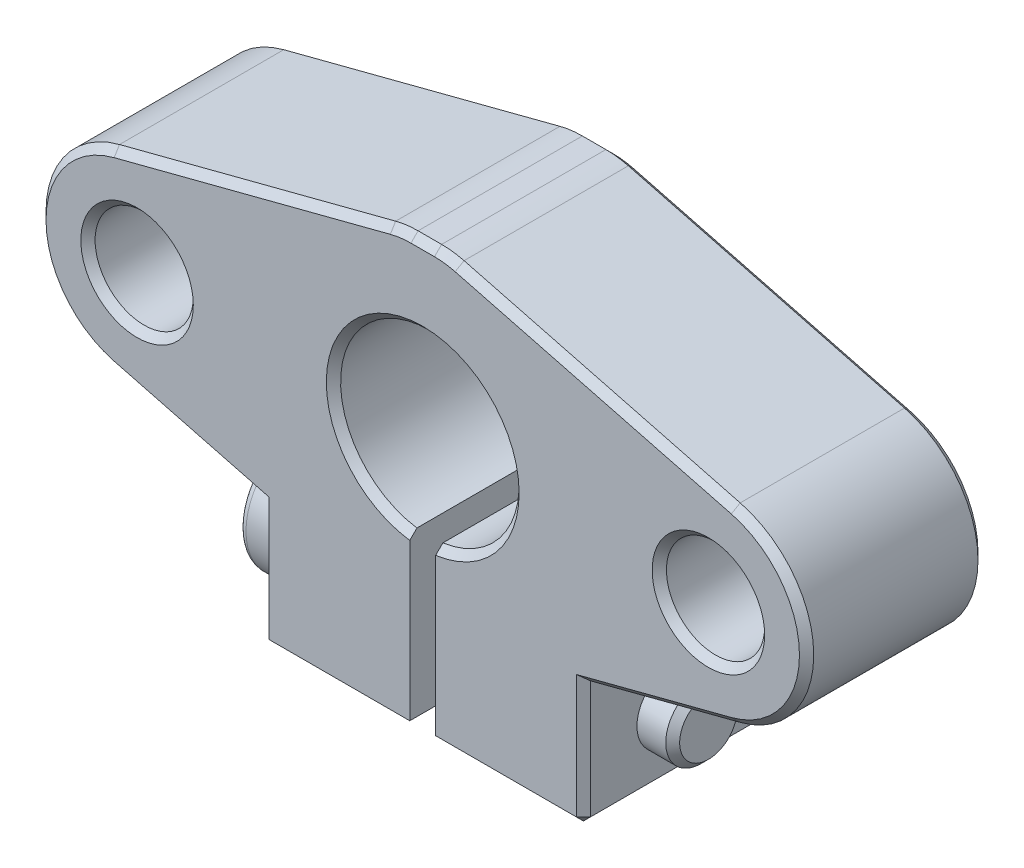
SolidWorks part; units mm, degrees
ref_plane "Спереди" through (0, 0, 0) normal (0, 0, 1) x (1, 0, 0)
ref_plane "Сверху" through (0, 0, 0) normal (0, 1, 0) x (1, 0, 0)
ref_plane "Справа" through (0, 0, 0) normal (1, 0, 0) x (0, 0, -1)
sketch "Эскиз2" plane through (0, 0, 0) normal (0, 0, 1) x (1, 0, 0)
  line L0 (-16, 0) -> (16, 0) construction
  line L1 (9, 7.5) -> (1.2976, 9.5)
  line L2 (9, 7.5) -> (17.3823, 5.3235)
  line L3 (0, 14.1459) -> (0, -18.2907) construction
  line L4 (9, -7.5) -> (17.3823, -5.3235)
  line L5 (-9, -14.5) -> (9, -14.5)
  line L6 (9, -14.5) -> (9, -7.5)
  line L7 (9, -11) -> (-9, -11) construction
  line L8 (1.2976, 9.5) -> (-1.2976, 9.5)
  line L9 (21.5, 0) -> (21.5, -6.4867) construction
  line L10 (0.725, -4.9472) -> (0.725, -14.5)
  line L11 (-21.5, 0) -> (-21.5, -6.4867) construction
  line L12 (-0.725, -4.9472) -> (-0.725, -14.5)
  line L13 (-9, -14.5) -> (-9, -7.5)
  line L14 (-9, -7.5) -> (-17.3823, -5.3235)
  line L15 (-9, 7.5) -> (-17.3823, 5.3235)
  line L16 (-9, 7.5) -> (-1.2976, 9.5)
  circle A0 centre (0, 0) radius 5
  circle A2 centre (16, 0) radius 2.75
  circle A3 centre (16, 0) radius 5.5
  circle A4 centre (-16, 0) radius 5.5
  circle A5 centre (-16, 0) radius 2.75
  point P27 (0, -11)
  point P33 (0, 9.5)
  point P35 (0, -14.5)
  dimension "D2" = 5.5
  dimension "D3" = 11
  dimension "D4" = 10
  dimension "D5" = 16
  dimension "D6" = 9
  dimension "D7" = 11
  dimension "D8" = 24
  dimension "D9" = 21.5
  dimension "D10" = 7
  dimension "D11" = 1.45
extrude "Бобышка-Вытянуть1" add sketch "Эскиз2" along normal blind 10 contours L15 A4 L14 L13 L5 L12 A0 L10 L6 L4 A3 L2 L1 L8 L16 | A3 A2 | A4 A5 region at (13.085, 6.0028, 0) region at (20.2274, 3.2699, 0) region at (-12.7301, 4.2274, 0)
sketch "Эскиз4" plane through (-9, 0, 0) normal (-1, 0, 0) x (0, 0, 1)
  line L0 (0, -14.5) -> (10, -7.5) construction
  circle A0 centre (5, -11) radius 2
  dimension "D1" = 4
fillet "Скругление1" radius 5 2 edges at (-1.2976, 9.5, 5) (1.2976, 9.5, 5)
chamfer "Фаска1" distance 0.4 angle 45 34 edges at (-13.25, 0, 10) (18.75, 0, 10) (0.725, -14.5, 5) (9, -14.5, 5) (-9, -14.5, 5) (-21.5, 0, 0) (-13.1911, -6.4117, 0) (-4.8625, -14.5, 0) (-9.649, 7.3315, 0) (0, 9.5, 0) (9.649, 7.3315, 0) (21.5, 0, 0) (13.1911, -6.4117, 0) (4.8625, -14.5, 0) (0, 5, 0) (-0.725, -14.5, 5) (0, 9.5, 10) (9.649, 7.3315, 10) (21.5, 0, 10) (13.1911, -6.4117, 10) (9, -11, 10) (4.8625, -14.5, 10) (0, 5, 10) (-4.8625, -14.5, 10) (-13.1911, -6.4117, 10) (-21.5, 0, 10) (-9.649, 7.3315, 10) (-1.2924, 9.4597, 0) (1.2924, 9.4597, 0) (1.2924, 9.4597, 10) (-1.2924, 9.4597, 10) (-9, -11, 10) (-13.25, 0, 0) (18.75, 0, 0)
sketch "Эскиз6" plane through (0, 0, 10) normal (0, 0, 1) x (1, 0, 0)
  line L0 (-8.6, -11) -> (-10.2537, -10.0452)
  line L1 (-10.2537, -10.0452) -> (-10.2537, -11.9548)
  line L2 (-10.2537, -11.9548) -> (-8.6, -11)
  line L3 (-9, -14.5) -> (-9, -7.5) construction
  point P5 (-9, -11)
  dimension "D1" = 0.4
extrude "Вырез-Вытянуть3" cut sketch "Эскиз6" against normal up to next
extrude "Вырез-Вытянуть1" cut sketch "Эскиз4" against normal through all contours A0
ref_plane "Плоскость1" through (0, 0, 5) normal (0, 0, 1) x (1, 0, 0)
sketch "Эскиз7" plane through (0, 0, 5) normal (0, 0, 1) x (1, 0, 0)
  line L0 (-8.6, -11) -> (14.2, -11) construction
  line L1 (-11.8, -11) -> (-11.8, -7.5)
  line L2 (-11.8, -7.5) -> (-9, -7.5)
  line L3 (-9, -7.5) -> (-9, -9)
  line L4 (-9, -9) -> (10.61, -9)
  line L5 (11, -9.39) -> (11, -11)
  line L6 (11, -11) -> (-11.8, -11)
  line L7 (11, -9.39) -> (10.61, -9)
  line L8 (-9, -10.7691) -> (-9, -7.5) construction
  line L9 (-8.3, 1.4588) -> (-8.3, -4.8912) construction
  line L10 (-3, 1.4588) -> (-3, -4.8912) construction
  line L11 (-49, 1.4588) -> (-49, -4.8912) construction
  dimension "D1" = 2.8
  dimension "D2" = 20
  dimension "D3" = 45
  dimension "D6" = 0.7
  dimension "D7" = 14
  dimension "D8" = 60
  dimension "D9" = 2
  dimension "D10" = 1.61
  dimension "D11" = 3.5
revolve "Повернуть1" add sketch "Эскиз7" angle 360 about L6
fillet "Скругление2" radius 0.4 1 edges at (-11.8, -7.5, 5)
sketch "Эскиз8" plane through (-11.8, 0, 0) normal (-1, 0, 0) x (0, 0, 1)
  line L1 (5, -9.2679) -> (3.5, -10.134)
  line L2 (3.5, -10.134) -> (3.5, -11.866)
  line L3 (3.5, -11.866) -> (5, -12.7321)
  line L4 (5, -12.7321) -> (6.5, -11.866)
  line L5 (6.5, -11.866) -> (6.5, -10.134)
  line L6 (6.5, -10.134) -> (5, -9.2679)
  circle A0 centre (5, -11) radius 1.5 construction
  dimension "D1" = 3
extrude "Вырез-Вытянуть4" cut sketch "Эскиз8" against normal blind 2.5
chamfer "Фаска2" distance 0.4 angle 45 12 edges at (-11.8, -9.701, 4.25) (-11.8, -11, 3.5) (-11.8, -12.299, 4.25) (-11.8, -12.299, 5.75) (-11.8, -11, 6.5) (-11.8, -9.701, 5.75) (-9.3, -11, 6.5) (-9.3, -12.299, 5.75) (-9.3, -12.299, 4.25) (-9.3, -11, 3.5) (-9.3, -9.701, 4.25) (-9.3, -9.701, 5.75)
ref_axis "Ось1" through (0, 0, 9.6) along (0, 0, -1)
